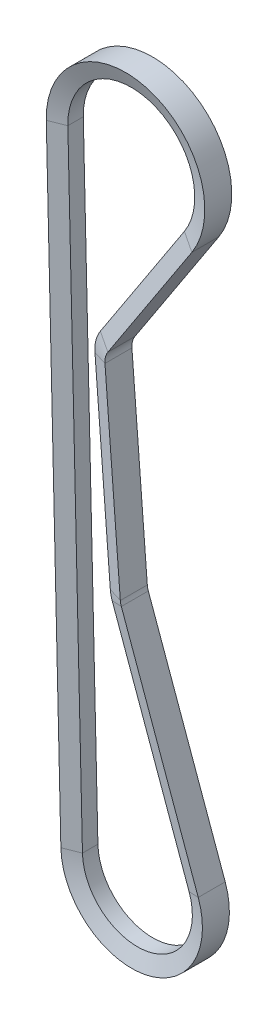
SolidWorks part; units mm, degrees
ref_plane "Front Plane" through (0, 0, 0) normal (0, 0, 1) x (1, 0, 0)
ref_plane "Top Plane" through (0, 0, 0) normal (0, 1, 0) x (1, 0, 0)
ref_plane "Right Plane" through (0, 0, 0) normal (1, 0, 0) x (0, 0, -1)
sketch "Sketch2" plane through (0, 0, 0) normal (0, 0, 1) x (1, 0, 0)
  line L0 (0, 0) -> (1, 0) construction
  line L1 (0, 0) -> (0, 1) construction
  line L12 (-24.9931, -0.5856) -> (-30.1461, 219.3336)
  line L14 (21.2761, 204.6583) -> (-8.4085, 159.2931)
  line L15 (-9.4258, 155.3236) -> (-3.9964, 85.5345)
  line L16 (-3.6397, 83.8751) -> (23.5207, 8.4722)
  arc A4 (-30.1461, 219.3336) -> (21.2761, 204.6583) centre (-2.1537, 219.9895) cw
  arc A7 (23.5207, 8.4722) -> (-24.9931, -0.5856) centre (0, 0) cw
  arc A8 (-8.4085, 159.2931) -> (-9.4258, 155.3236) centre (-3.0949, 155.8162) ccw
  arc A9 (-3.9964, 85.5345) -> (-3.6397, 83.8751) centre (2.3345, 86.027) ccw
ref_plane "Plane4" through (23.5207, 8.4722, 0) normal (0.3389, -0.9408, 0) x (-0.9408, -0.3389, 0)
sketch "Sketch3" plane through (23.5207, 8.4722, 0) normal (0.3389, -0.9408, 0) x (-0.9408, -0.3389, 0)
  line L0 (0, -4.7625) -> (0, 4.7625)
  line L1 (0, -4.7625) -> (5.588, -2.7286)
  line L2 (5.588, -2.7286) -> (5.588, 2.7286)
  line L3 (5.588, 2.7286) -> (0, 4.7625)
  line L4 (0, 0) -> (5.588, 0) construction
  dimension "D1" = 9.525
  dimension "D2" = 5.588
  dimension "D3" = 40
sweep "Sweep1" add profiles "Sketch3" path "Sketch2"
